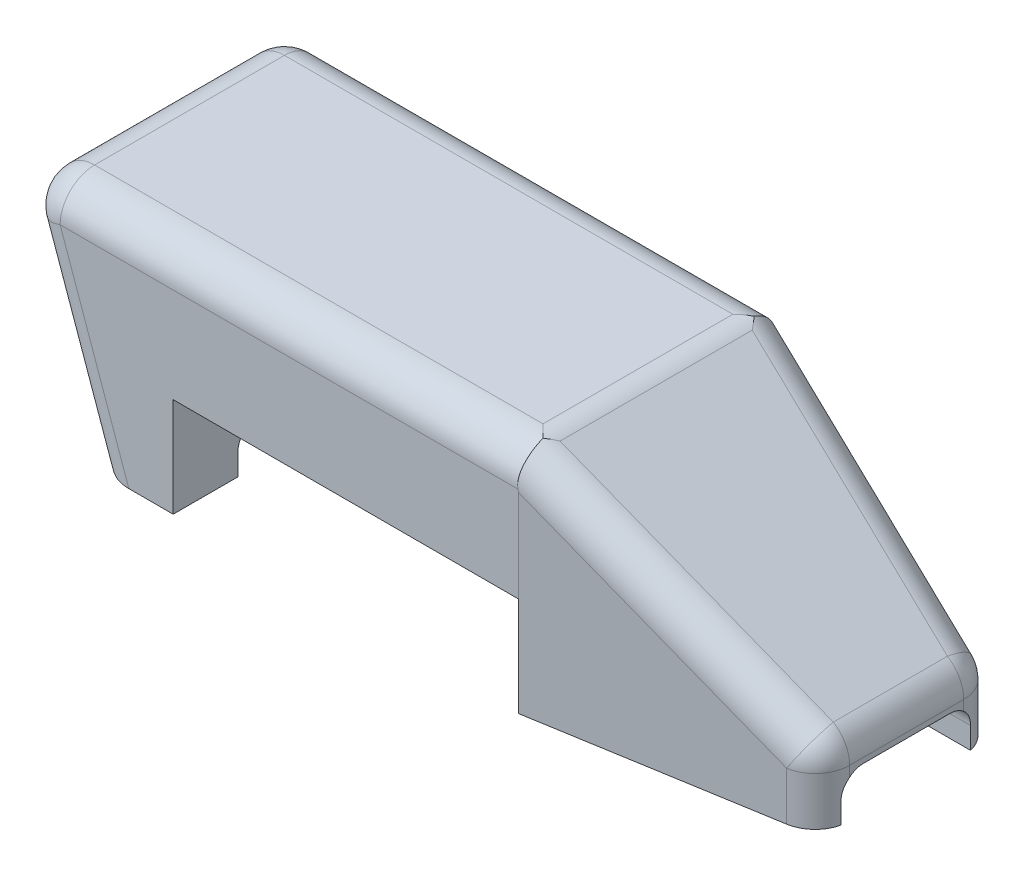
SolidWorks part; units mm, degrees
ref_plane "Front Plane" through (0, 0, 0) normal (0, 0, 1) x (1, 0, 0)
ref_plane "Top Plane" through (0, 0, 0) normal (0, 1, 0) x (1, 0, 0)
ref_plane "Right Plane" through (0, 0, 0) normal (1, 0, 0) x (0, 0, -1)
sketch "Sketch1" plane through (0, 0, 0) normal (0, 1, 0) x (1, 0, 0)
  line L1 (0, 60) -> (140, 60)
  line L2 (0, 60) -> (0, 0)
  line L3 (0, 0) -> (140, 0)
  line L4 (140, 60) -> (140, 0)
  dimension "D1" = 140
  dimension "D2" = 60
extrude "Boss-Extrude2" add sketch "Sketch1" along normal blind 30
sketch "Sketch2" plane through (0, 0, 0) normal (-1, 0, 0) x (0, 0, 1)
  line L0 (-60, 0) -> (0, 0) construction
  line L1 (-51, 0) -> (-9, 0)
  line L2 (-51, 0) -> (-51, 23)
  line L3 (-51, 23) -> (-9, 23)
  line L4 (-9, 0) -> (-9, 23)
  dimension "D1" = 42
  dimension "D2" = 9
  dimension "D3" = 23
extrude "Cut-Extrude1" cut sketch "Sketch2" against normal blind 80
sketch "Sketch3" plane through (0, 0, 0) normal (0, -1, 0) x (1, 0, 0)
  line L0 (0, 0) -> (140, 0) construction
  line L1 (80, 0) -> (140, 0)
  line L2 (80, 0) -> (80, -60)
  line L3 (80, -60) -> (140, -60)
  line L4 (140, 0) -> (140, -60)
  line L5 (80, -51) -> (80, -9) construction
extrude "Boss-Extrude3" add sketch "Sketch3" along normal blind 23
sketch "Sketch4" plane through (0, 0, 0) normal (0, 0, 1) x (1, 0, 0)
  line L0 (140, -7.3412) -> (80, 30)
  line L1 (140, 30) -> (140, -23) construction
  line L2 (0, 30) -> (140, 30) construction
  line L3 (80, 30) -> (140, 30)
  line L4 (140, 30) -> (140, -7.3412)
  dimension "D1" = 37.3412
extrude "Cut-Extrude6" cut sketch "Sketch4" against normal through all
sketch "Sketch15" plane through (0, 0, 0) normal (-1, 0, 0) x (0, 0, 1)
  line L1 (-60, 0) -> (0, 0)
  line L2 (-60, 0) -> (-60, 30)
  line L3 (-60, 30) -> (0, 30)
  line L4 (0, 0) -> (0, 30)
extrude "Boss-Extrude9" add sketch "Sketch15" along normal blind 20
sketch "Sketch16" plane through (0, 0, 0) normal (0, -1, 0) x (1, 0, 0)
  line L0 (80, -60) -> (-20, -60) construction
  line L1 (-20, 0) -> (0, 0)
  line L2 (-20, 0) -> (-20, -60)
  line L3 (-20, -60) -> (0, -60)
  line L4 (0, 0) -> (0, -60)
extrude "Boss-Extrude10" add sketch "Sketch16" along normal blind 23
sketch "Sketch17" plane through (0, -23, 0) normal (0, -1, 0) x (1, 0, 0)
  line L0 (80, -60) -> (140, -50)
  line L1 (140, -60) -> (140, 0) construction
  line L2 (140, -50) -> (140, -60)
  line L3 (140, -60) -> (80, -60)
  dimension "D1" = 10
extrude "Cut-Extrude9" cut sketch "Sketch17" against normal through all
sketch "Sketch18" plane through (0, -23, 0) normal (0, -1, 0) x (1, 0, 0)
  line L0 (80, 0) -> (140, -10)
  line L1 (140, -50) -> (140, 0) construction
  line L2 (140, -10) -> (140, 0)
  line L3 (140, 0) -> (80, 0)
  dimension "D1" = 10
extrude "Cut-Extrude11" cut sketch "Sketch18" against normal through all
sketch "Sketch20" plane through (0, 0, -60) normal (0, 0, -1) x (-1, 0, 0)
  line L0 (-80, 30) -> (20, 30) construction
  line L1 (20, -23) -> (37.5306, -23)
  line L2 (20, -23) -> (20, 30)
  line L3 (20, 30) -> (37.5306, 30)
  line L4 (37.5306, -23) -> (37.5306, 30)
extrude "Boss-Extrude11" add sketch "Sketch20" against normal through all
sketch "Sketch21" plane through (0, 0, -60) normal (0, 0, -1) x (-1, 0, 0)
  line L0 (18.7653, -23) -> (37.5306, 30)
  line L1 (37.5306, -23) -> (0, -23) construction
  line L2 (37.5306, 30) -> (37.5306, -23)
  line L3 (37.5306, -23) -> (18.7653, -23)
extrude "Cut-Extrude12" cut sketch "Sketch21" against normal through all
fillet "Fillet8" radius 8 7 edges at (-18.7653, -23, -30) (-28.1479, 3.5, 0) (-28.1479, 3.5, -60) (-37.5306, 30, -30) (21.2347, 30, 0) (21.2347, 30, -60) (80, 30, -30)
fillet "Fillet9" radius 8 5 edges at (140, -15.1706, -50) (140, -15.1706, -10) (140, -7.3412, -30) (113.2142, 9.3291, -54.4643) (113.2142, 9.3291, -5.5357)
sketch "Sketch22" plane through (80, 0, 0) normal (-1, 0, 0) x (0, 0, 1)
  line L0 (0, -23) -> (-60, -23) construction
  line L1 (-45, -23) -> (-15, -23)
  line L2 (-45, -23) -> (-45, -13)
  line L3 (-45, -13) -> (-15, -13)
  line L4 (-15, -23) -> (-15, -13)
  dimension "D1" = 15
  dimension "D2" = 15
  dimension "D3" = 10
extrude "Cut-Extrude13" cut sketch "Sketch22" against normal through all
fillet "Fillet11" radius 5 2 edges at (109.9001, -13, -45) (109.9001, -13, -15)
sketch "Sketch23" plane through (0, -13, 0) normal (0, -1, 0) x (1, 0, 0)
  line L0 (140, -20) -> (80, -20) construction
  line L1 (80, -40) -> (88, -40)
  line L2 (80, -40) -> (80, -20)
  line L3 (80, -20) -> (88, -20)
  line L4 (88, -40) -> (88, -20)
  dimension "D1" = 8
extrude "Cut-Extrude14" cut sketch "Sketch23" against normal blind 35
sketch "Sketch24" plane through (0, 0, 0) normal (1, 0, 0) x (0, 0, -1)
  line L0 (60, -23) -> (0, -23) construction
  line L1 (15, -23) -> (45, -23)
  line L2 (15, -23) -> (15, -13)
  line L3 (15, -13) -> (45, -13)
  line L4 (45, -23) -> (45, -13)
  dimension "D1" = 15
  dimension "D2" = 15
  dimension "D3" = 10
extrude "Cut-Extrude15" cut sketch "Sketch24" against normal blind 35
fillet "Fillet12" radius 5 2 edges at (-11.153, -13, -45) (-11.153, -13, -15)
